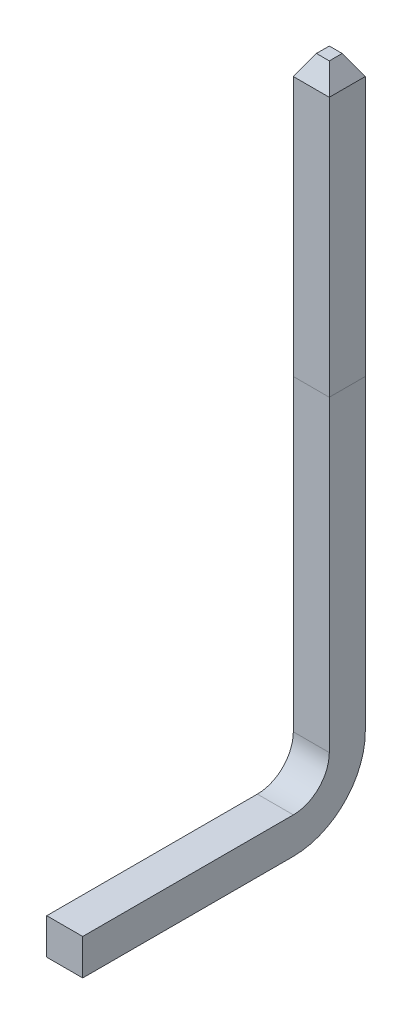
SolidWorks part; units mm, degrees
material "1060 Alloy"
ref_plane "Front Plane" through (0, 0, 0) normal (0, 0, 1) x (1, 0, 0)
ref_plane "Top Plane" through (0, 0, 0) normal (0, 1, 0) x (1, 0, 0)
ref_plane "Right Plane" through (0, 0, 0) normal (1, 0, 0) x (0, 0, -1)
sketch "Sketch1" plane through (0, 0, 0) normal (1, 0, 0) x (0, 0, -1)
  line L11 (8.9789, 2.286) -> (8.9789, 20.955)
  line L12 (8.9789, 20.955) -> (7.8359, 20.955)
  line L13 (7.8359, 20.955) -> (7.8359, 2.286)
  line L14 (0, 0) -> (6.6929, 0)
  line L18 (6.6929, 1.143) -> (0, 1.143)
  line L19 (0, 1.143) -> (0, 0)
  arc A2 (6.6929, 0) -> (8.9789, 2.286) centre (6.6929, 2.286) ccw
  arc A3 (6.6929, 1.143) -> (7.8359, 2.286) centre (6.6929, 2.286) ccw
  dimension "D4" = 2.286
  dimension "D1" = 1.143
  dimension "D2" = 8.9789
  dimension "D3" = 20.955
extrude "Boss-Extrude1" add sketch "Sketch1" along normal blind 1.143
sketch "Sketch2" plane through (1.143, 0, 0) normal (1, 0, 0) x (0, 0, -1)
  line L0 (7.8359, 12.065) -> (8.9789, 12.065)
  line L1 (7.8359, 20.955) -> (7.8359, 2.286) construction
  line L2 (8.9789, 2.286) -> (8.9789, 20.955) construction
  line L3 (8.9789, 20.955) -> (7.8359, 20.955) construction
  dimension "D1" = 8.89
split line "Split Line1"
chamfer "Chamfer1" distance 0.635 angle 30 4 edges at (0.5715, 20.955, -8.9789) (1.143, 20.955, -8.4074) (0.5715, 20.955, -7.8359) (0, 20.955, -8.4074) first distance on face at (0.5715, 16.51, -8.9789) first distance on face at (1.143, 16.51, -8.4074) first distance on face at (0.5715, 16.51, -7.8359) first distance on face at (0, 16.51, -8.4074)
sketch "Sketch3" plane through (0, 0, 0) normal (0, 0, 1) x (1, 0, 0)
  line L0 (1.143, 0) -> (0, 1.143) construction
  line L1 (0.5715, 0.5715) -> (0, 0) construction
ref_axis "Axis1" through (0.5715, 0.5715, 0) along (0, 0, -1)
scale "Scale1" scale about centroid uniform scaling yes scale factor 0.654
